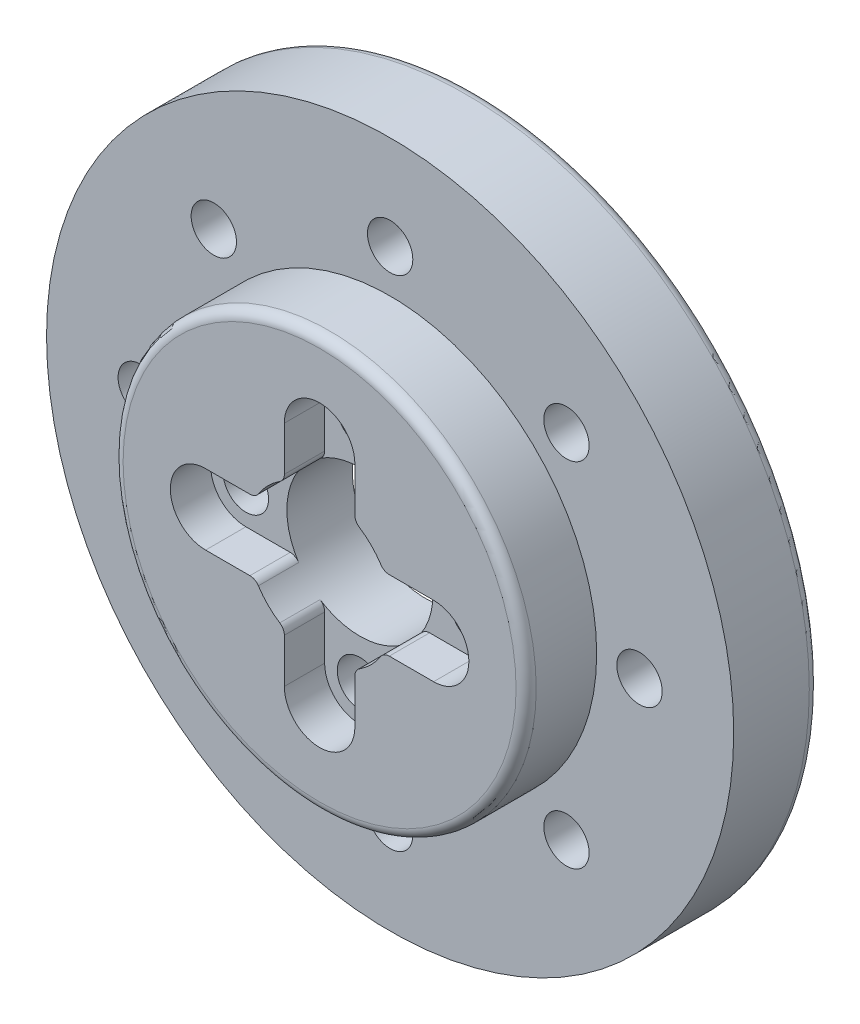
SolidWorks part; units mm, degrees
ref_plane "Front Plane" through (0, 0, 0) normal (0, 0, 1) x (1, 0, 0)
ref_plane "Top Plane" through (0, 0, 0) normal (0, 1, 0) x (1, 0, 0)
ref_plane "Right Plane" through (0, 0, 0) normal (1, 0, 0) x (0, 0, -1)
sketch "Sketch1" plane through (0, 0, 0) normal (0, 0, 1) x (1, 0, 0)
  circle A0 centre (0, 0) radius 34.1
  dimension "D1" = 68.2
extrude "Boss-Extrude1" add sketch "Sketch1" along normal mid plane 3.5
sketch "Sketch4" plane through (0, 0, 1.75) normal (0, 0, 1) x (1, 0, 0)
  circle A0 centre (0, 0) radius 28.5
  dimension "D1" = 57
extrude "Boss-Extrude2" add sketch "Sketch4" along normal blind 2
sketch "Sketch5" plane through (0, 0, -1.75) normal (0, 0, -1) x (-1, 0, 0)
  circle A0 centre (0, 0) radius 16.25
  circle A1 centre (0, 0) radius 34.1 construction
  circle A2 centre (0, 0) radius 34.1
  dimension "D1" = 32.5
extrude "Boss-Extrude3" add sketch "Sketch5" along normal blind 5
sketch "Sketch3" plane through (0, 0, 1.75) normal (0, 0, 1) x (1, 0, 0)
  circle A8 centre (0, 0) radius 11.3137 construction
  circle A9 centre (0, 11.3137) radius 2.25
  circle A11 centre (11.3137, 0) radius 2.25
  circle A13 centre (0, -11.3137) radius 2.25
  circle A15 centre (-11.3137, 0) radius 2.25
  point P21 (0, 0)
  dimension "D3" = 22.6274
  dimension "D4" = 4.5
  dimension "D5" = 4
extrude "Cut-Extrude2" cut sketch "Sketch3" against normal through all both and the other way through all
sketch "Sketch2" plane through (0, 0, 1.75) normal (0, 0, 1) x (1, 0, 0)
  circle A0 centre (0, 0) radius 7.25
  dimension "D1" = 14.5
extrude "Cut-Extrude1" cut sketch "Sketch2" along normal through all both and the other way through all
sketch "Sketch6" plane through (0, 0, 3.75) normal (0, 0, 1) x (1, 0, 0)
  circle A0 centre (0, 24.75) radius 2.25
  dimension "D1" = 4.5
  dimension "D2" = 24.75
extrude "Cut-Extrude3" cut sketch "Sketch6" against normal through all both and the other way through all
pattern_circular "CirPattern1" count 8 over 360 about axis through (0, 0, 1.75) along (0, 0, -1) of "Cut-Extrude3"
sketch "Sketch7" plane through (0, 0, 3.75) normal (0, 0, 1) x (1, 0, 0)
  circle A0 centre (0, 0) radius 20.5
  circle A5 centre (0, -11.3137) radius 2.25 construction
  circle A6 centre (11.3137, 0) radius 2.25 construction
  circle A7 centre (0, 11.3137) radius 2.25 construction
  circle A8 centre (-11.3137, 0) radius 2.25 construction
  circle A9 centre (0, 0) radius 7.25 construction
  circle A10 centre (0, -11.3137) radius 2.25
  circle A11 centre (11.3137, 0) radius 2.25
  circle A12 centre (0, 11.3137) radius 2.25
  circle A13 centre (-11.3137, 0) radius 2.25
  circle A14 centre (0, 0) radius 7.25
  dimension "D1" = 41
extrude "Boss-Extrude4" add sketch "Sketch7" along normal blind 5
sketch "Sketch8" plane through (0, 0, 1.75) normal (0, 0, 1) x (1, 0, 0)
  circle A0 centre (0, 0) radius 28.5 construction
  circle A1 centre (0, 0) radius 34.1
  circle A2 centre (0, 0) radius 34.1
  circle A3 centre (0, 0) radius 28.5
  dimension "D1" = 0
extrude "Boss-Extrude5" add sketch "Sketch8" along normal up to surface (2 mm away) up to face at (20.5, 0, 3.75)
sketch "Sketch10" plane through (0, 0, 3.75) normal (0, 0, 1) x (1, 0, 0)
  circle A0 centre (0, 0) radius 20.5 construction
  circle A1 centre (0, 0) radius 34.1
  circle A2 centre (0, 0) radius 34.1
  circle A3 centre (0, 0) radius 20.5
  dimension "D1" = 0
extrude "Cut-Extrude4" cut sketch "Sketch10" against normal blind 2
sketch "Sketch11" plane through (0, 0, 8.75) normal (0, 0, 1) x (1, 0, 0)
  line L0 (-11.3137, 3.5) -> (-3.5, 3.5)
  line L1 (-3.5, 3.5) -> (-3.5, 11.3137)
  line L2 (3.5, 11.3137) -> (3.5, 3.5)
  line L3 (3.5, 3.5) -> (11.3137, 3.5)
  line L4 (11.3137, -3.5) -> (3.5, -3.5)
  line L5 (3.5, -3.5) -> (3.5, -11.3137)
  line L6 (-3.5, -11.3137) -> (-3.5, -3.5)
  line L7 (-3.5, -3.5) -> (-11.3137, -3.5)
  circle A0 centre (-11.3137, 0) radius 2.25 construction
  circle A1 centre (0, -11.3137) radius 2.25 construction
  circle A2 centre (11.3137, 0) radius 2.25 construction
  circle A3 centre (0, 11.3137) radius 2.25 construction
  circle A4 centre (-11.3137, 0) radius 2.25 construction
  circle A5 centre (0, -11.3137) radius 2.25 construction
  circle A6 centre (11.3137, 0) radius 2.25 construction
  circle A7 centre (0, 11.3137) radius 2.25 construction
  arc A8 (-3.5, -11.3137) -> (3.5, -11.3137) centre (0, -11.3137) ccw
  arc A9 (11.3137, -3.5) -> (11.3137, 3.5) centre (11.3137, 0) ccw
  arc A10 (3.5, 11.3137) -> (-3.5, 11.3137) centre (0, 11.3137) ccw
  arc A11 (-11.3137, 3.5) -> (-11.3137, -3.5) centre (-11.3137, 0) ccw
  point P27 (-3.5, -3.5)
  dimension "D1" = 7
extrude "Cut-Extrude5" cut sketch "Sketch11" against normal blind 4
fillet "Fillet1" radius 1 8 edges at (-6.3492, -3.5, 6.75) (-3.5, -6.3492, 6.75) (3.5, -6.3492, 6.75) (6.3492, -3.5, 6.75) (6.3492, 3.5, 6.75) (3.5, 6.3492, 6.75) (-3.5, 6.3492, 6.75) (-6.3492, 3.5, 6.75)
sketch "Sketch12" plane through (0, 0, -6.75) normal (0, 0, -1) x (-1, 0, 0)
  circle A0 centre (0, 24.75) radius 3.5
  circle A1 centre (17.5009, 17.5009) radius 3.5
  circle A2 centre (24.75, 0) radius 3.5
  circle A3 centre (17.5009, -17.5009) radius 3.5
  circle A4 centre (0, -24.75) radius 3.5
  circle A5 centre (-17.5009, -17.5009) radius 3.5
  circle A6 centre (-24.75, 0) radius 3.5
  circle A7 centre (-17.5009, 17.5009) radius 3.5
  point P4 (-17.0849, 11.7087)
  point P5 (0, 0)
  point P19 (0, 0)
  dimension "D1" = 7
  dimension "D2" = 8
extrude "Cut-Extrude6" cut sketch "Sketch12" against normal blind 3
fillet "Fillet2" radius 1 2 edges at (20.5, 0, 8.75) (-34.1, 0, -6.75)
